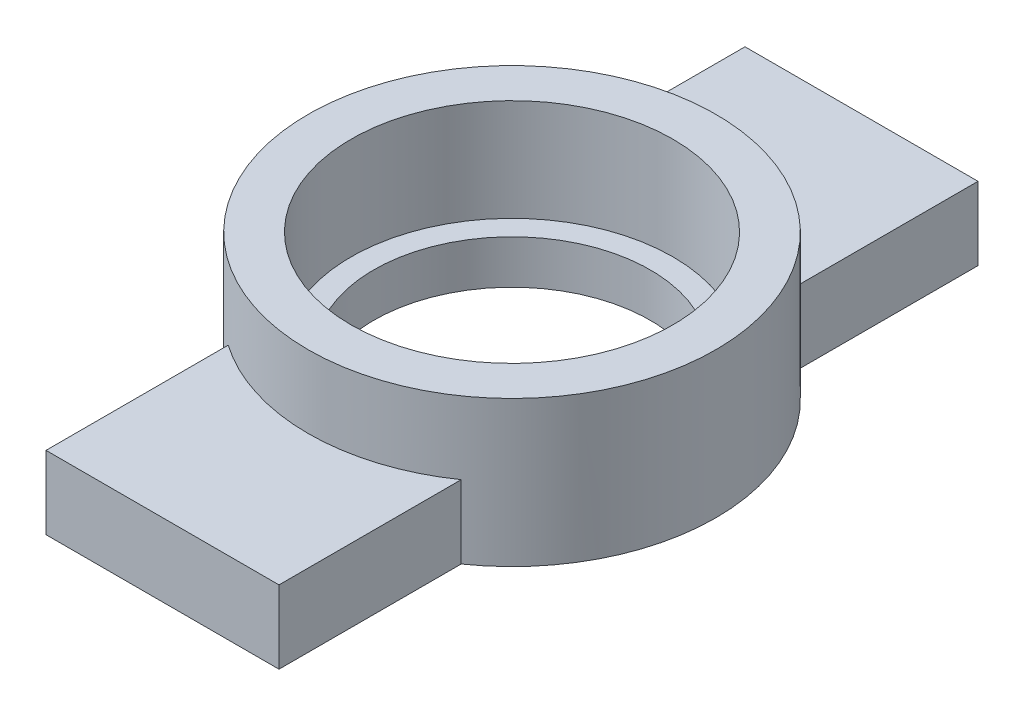
SolidWorks part; units mm, degrees
ref_plane "Front Plane" through (0, 0, 0) normal (0, 0, 1) x (1, 0, 0)
ref_plane "Top Plane" through (0, 0, 0) normal (0, 1, 0) x (1, 0, 0)
ref_plane "Right Plane" through (0, 0, 0) normal (1, 0, 0) x (0, 0, -1)
sketch "Sketch1" plane through (0, 0, 0) normal (0, 1, 0) x (1, 0, 0)
  circle A0 centre (0, 0) radius 9.5
  circle A1 centre (0, 0) radius 11.05
  circle A2 centre (0, 0) radius 14
  dimension "D1" = 22.1
  dimension "D2" = 19
  dimension "D3" = 28
extrude "Boss-Extrude1" add sketch "Sketch1" along normal blind 10 contours A2 A1 region at (-13.604, 0, 0)
extrude "Boss-Extrude2" add sketch "Sketch1<3>" along normal blind 3 contours A0 | A1
sketch "Sketch1<3>" plane through (0, 0, 0) normal (0, 1, 0) x (1, 0, 0) same geometry as "Sketch1"
ref_plane "Plane1" through (0, 0, 14) normal (0, 0, 1) x (1, 0, 0)
sketch "Sketch4" plane through (0, 0, 14) normal (0, 0, 1) x (1, 0, 0)
  line L0 (-14, 0) -> (14, 0) construction
  line L1 (-8, 0) -> (8, 0)
  line L2 (-8, 0) -> (-8, 5.0164)
  line L3 (-8, 5.0164) -> (8, 5.0164)
  line L4 (8, 0) -> (8, 5.0164)
  point P6 (0, 0)
  dimension "D1" = 16
  dimension "D2" = 5.0164
extrude "Boss-Extrude3" add sketch "Sketch4" along normal blind 10 and the other way up to surface other way up to face at (0, 10, 14)
mirror "Mirror1" about plane through (0, 0, 0) normal (0, 0, 1) of "Boss-Extrude3"
